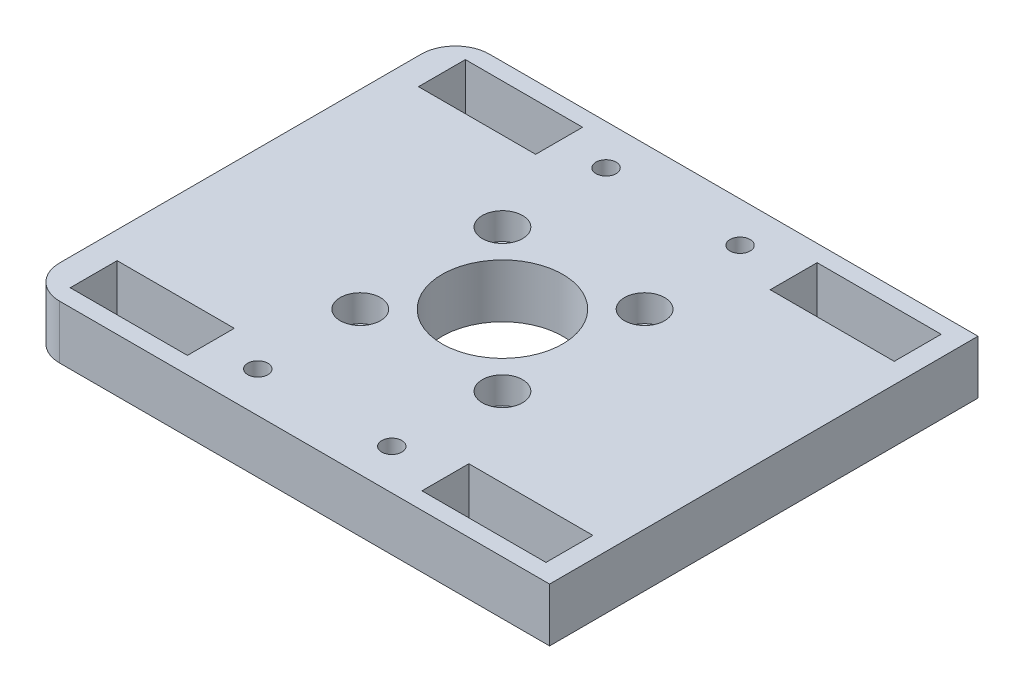
SolidWorks part; units mm, degrees
ref_plane "Front" through (0, 0, 0) normal (0, 0, 1) x (1, 0, 0)
ref_plane "Top" through (0, 0, 0) normal (0, 1, 0) x (1, 0, 0)
ref_plane "Right" through (0, 0, 0) normal (1, 0, 0) x (0, 0, -1)
sketch "Sketch1" plane through (0, 0, 0) normal (0, 1, 0) x (1, 0, 0)
  line L0 (-108.7101, 0) -> (152.735, 0) construction
  line L1 (0, 79.771) -> (0, -208.6666) construction
  line L2 (0, 0) -> (10.6066, 10.6066) construction
  line L3 (0, 0) -> (-10.6066, 10.6066) construction
  line L4 (0, 0) -> (10.6066, -10.6066) construction
  line L5 (0, 0) -> (-10.6066, -10.6066) construction
  line L7 (-33.9225, 31.9861) -> (38.983, 31.9861)
  line L8 (-39.017, 26.8916) -> (-39.017, -27.062)
  line L9 (-34.065, -32.0139) -> (39.0509, -32.0139)
  line L11 (-39.017, 31.9861) -> (39.0509, -32.0139) construction
  line L12 (-39.017, -32.0139) -> (38.983, 31.9861) construction
  line L16 (-35.017, 22.4861) -> (-17.527, 22.4861)
  line L20 (-17.527, 22.4861) -> (-17.527, 29.4861)
  line L21 (17.473, 29.4861) -> (17.473, 22.4861)
  line L22 (35.983, 29.4861) -> (35.983, 22.4861)
  line L23 (17.473, 29.4861) -> (35.983, 29.4861)
  line L24 (17.473, 22.4861) -> (35.983, 22.4861)
  line L25 (35.983, -29.4861) -> (35.983, -22.4861)
  line L26 (-35.017, 22.4861) -> (-35.017, 29.4861)
  line L27 (17.473, -29.4861) -> (35.983, -29.4861)
  line L28 (-35.017, 29.4861) -> (-17.527, 29.4861)
  line L29 (17.473, -22.4861) -> (35.983, -22.4861)
  line L30 (17.473, -29.4861) -> (17.473, -22.4861)
  line L31 (-35.017, -22.4861) -> (-17.527, -22.4861)
  line L32 (-35.017, -22.4861) -> (-35.017, -29.4861)
  line L33 (-17.527, -22.4861) -> (-17.527, -29.4861)
  line L34 (-35.017, -29.4861) -> (-17.527, -29.4861)
  line L35 (38.983, 31.9861) -> (39.0509, -32.0139)
  circle A0 centre (0, 0) radius 9
  circle A1 centre (10.6066, 10.6066) radius 1.5
  circle A2 centre (-10.6066, 10.6066) radius 1.5
  circle A3 centre (10.6066, -10.6066) radius 1.5
  circle A4 centre (-10.6066, -10.6066) radius 1.5
  arc A6 (-39.017, -27.062) -> (-34.065, -32.0139) centre (-34.065, -27.062) ccw
  arc A8 (-33.9225, 31.9861) -> (-39.017, 26.8916) centre (-33.9225, 26.8916) ccw
  dimension "D1" = 18
  dimension "D4" = 3
  dimension "D5" = 64
  dimension "D2" = 15
  dimension "D3" = 45
  dimension "D6" = 78
  dimension "D9" = 4
  dimension "D7" = 17.49
  dimension "D8" = 35
  dimension "D10" = 71
  dimension "D12" = 2.5
  dimension "D13" = 7
extrude "Boss-Extrude1" add sketch "Sketch1" along normal blind 8
sketch "Sketch2" plane through (0, 8, 0) normal (0, 1, 0) x (1, 0, 0)
  circle A0 centre (10.6066, 10.6066) radius 3
  circle A1 centre (10.6066, -10.6066) radius 3
  circle A2 centre (-10.6066, -10.6066) radius 3
  circle A3 centre (-10.6066, 10.6066) radius 3
  dimension "D1" = 6
  dimension "D2" = 6
  dimension "D3" = 6
  dimension "D4" = 6
extrude "Cut-Extrude1" cut sketch "Sketch2" against normal blind 4
sketch "Sketch5" plane through (0, 0, 0) normal (0, -1, 0) x (1, 0, 0)
  line L0 (-46.4753, 0) -> (52.0337, 0) construction
  line L1 (0, 40.8545) -> (0, -37.3159) construction
  line L2 (-17.527, 25.9861) -> (17.473, 25.9861) construction
  line L3 (-17.527, 29.4861) -> (-17.527, 22.4861) construction
  line L4 (17.473, 22.4861) -> (17.473, 29.4861) construction
  circle A0 centre (-10.5231, 25.9861) radius 1.5
  circle A1 centre (9.473, 25.9861) radius 1.5
  circle A2 centre (-10.5231, 25.9861) radius 3
  circle A3 centre (9.473, 25.9861) radius 3
  circle A4 centre (9.473, -25.9861) radius 3
  circle A5 centre (9.473, -25.9861) radius 1.5
  circle A6 centre (-10.5231, -25.9861) radius 3
  circle A7 centre (-10.5231, -25.9861) radius 1.5
  dimension "D1" = 3
  dimension "D2" = 3
  dimension "D3" = 6
  dimension "D4" = 6
  dimension "D5" = 7.0039
  dimension "D6" = 8
extrude "Cut-Extrude3" cut sketch "Sketch5" against normal through all contours A0 | A1 | A5 | A7 region at (-10.5231, 0, 25.9861) region at (9.473, 0, 25.9861) region at (9.473, 0, -25.9861) region at (-10.5231, 0, -25.9861)
extrude "Cut-Extrude4" cut sketch "Sketch5<3>" against normal blind 4 contours A6 A7 | A4 A5 | A3 A1 | A2 A0 region at (-13.4382, 0, 25.9861) region at (6.5579, 0, 25.9861) region at (6.5579, 0, -25.9861) region at (-13.4382, 0, -25.9861)
sketch "Sketch5<3>" plane through (0, 0, 0) normal (0, -1, 0) x (1, 0, 0) same geometry as "Sketch5"
